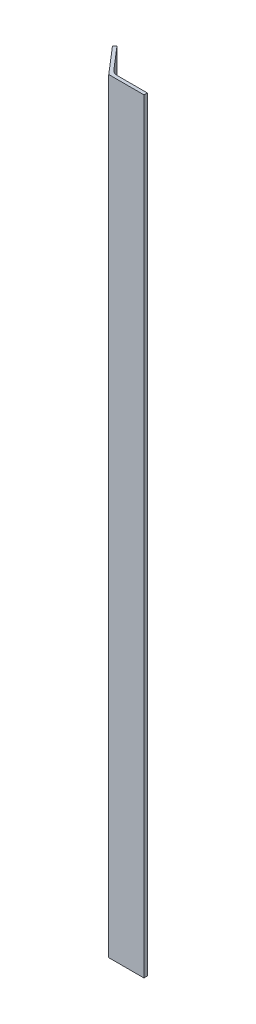
SolidWorks part; units mm, degrees
ref_plane "Спереди" through (0, 0, 0) normal (0, 0, 1) x (1, 0, 0)
ref_plane "Сверху" through (0, 0, 0) normal (0, 1, 0) x (1, 0, 0)
ref_plane "Справа" through (0, 0, 0) normal (1, 0, 0) x (0, 0, -1)
sketch "Эскиз1" plane through (0, 0, 0) normal (0, 1, 0) x (1, 0, 0)
  line L0 (-17.7667, 14.446) -> (-16.3084, 15.7)
  line L1 (-0.9318, 0.4869) -> (17.1228, 0.4869)
  line L2 (-16.3084, 15.7) -> (-4.7229, 2.2269)
  line L3 (-17.7667, 14.446) -> (-4.0435, -1.5131)
  line L4 (-4.0435, -1.5131) -> (17.1228, -1.5131)
  line L5 (17.1228, -1.5131) -> (17.1228, 0.4869)
  arc A0 (-0.9318, 0.4869) -> (-4.7229, 2.2269) centre (-0.9318, 5.4869) cw
  dimension "D1" = 5
extrude "Вытянуть1" add sketch "Эскиз1" along normal blind 460 from offset 40
sketch "Эскиз2" plane through (0, 0, 1.5131) normal (0, 0, 1) x (1, 0, 0)
  line L1 (19.8228, 310.9032) -> (5.9287, 310.9032)
  line L2 (19.8228, 310.9032) -> (19.8228, 135.9413)
  line L3 (19.8228, 135.9413) -> (5.9287, 135.9413)
  line L4 (5.9287, 310.9032) -> (5.9287, 135.9413)
extrude "Вырез-Вытянуть1" [suppressed] cut sketch "Эскиз2" against normal through all
